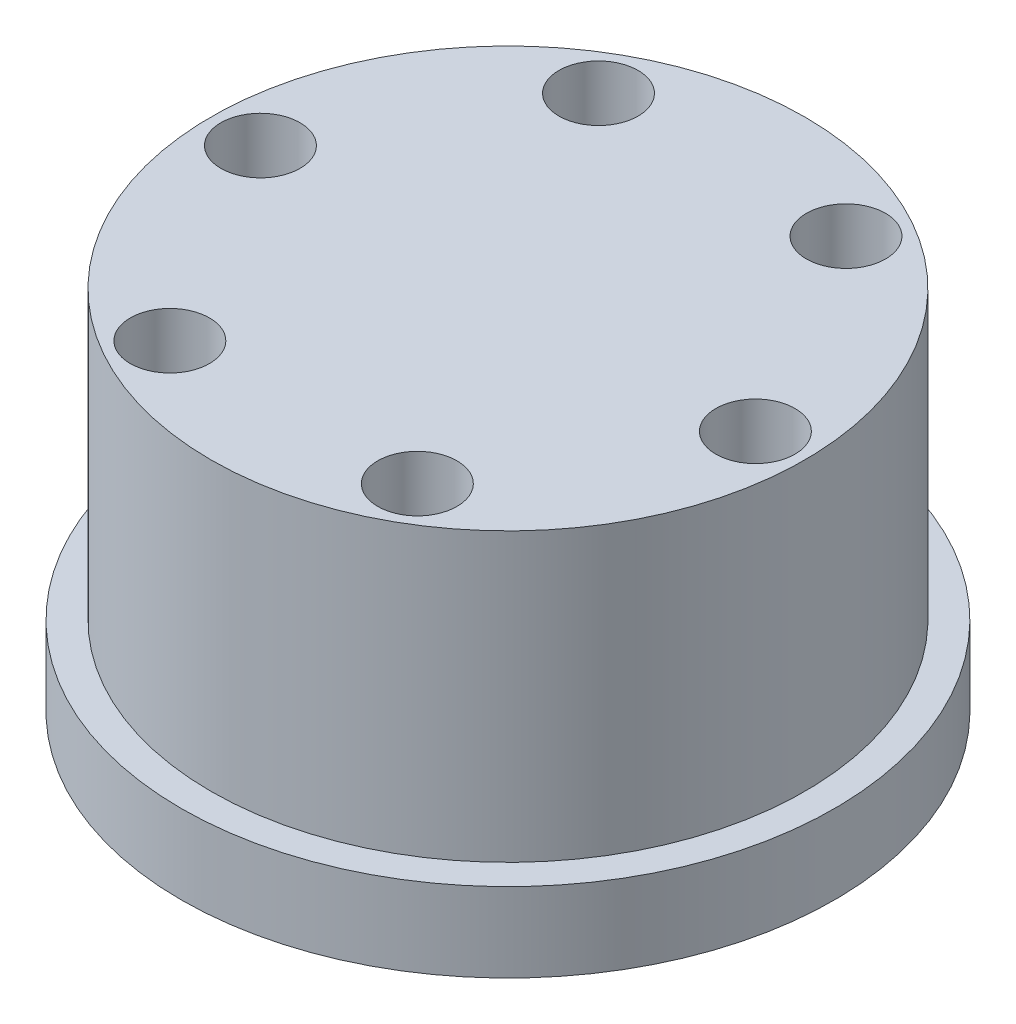
SolidWorks part; units mm, degrees
ref_plane "Front Plane" through (0, 0, 0) normal (0, 0, 1) x (1, 0, 0)
ref_plane "Top Plane" through (0, 0, 0) normal (0, 1, 0) x (1, 0, 0)
ref_plane "Right Plane" through (0, 0, 0) normal (1, 0, 0) x (0, 0, -1)
sketch "Sketch1" plane through (0, 0, 0) normal (0, 1, 0) x (1, 0, 0)
  circle A0 centre (0, 0) radius 16.5
  circle A1 centre (0, 0) radius 12.5 construction
  circle A2 centre (0, 12.5) radius 1.5
  circle A3 centre (10.8253, 6.25) radius 1.5
  circle A4 centre (10.8253, -6.25) radius 1.5
  circle A5 centre (0, -12.5) radius 1.5
  circle A6 centre (-10.8253, -6.25) radius 1.5
  circle A7 centre (-10.8253, 6.25) radius 1.5
  point P19 (0, 0)
  dimension "D1" = 33
  dimension "D2" = 25
  dimension "D3" = 3
  dimension "D4" = 6
extrude "Boss-Extrude1" add sketch "Sketch1" along normal blind 4
sketch "Sketch2" plane through (0, 4, 0) normal (0, 1, 0) x (1, 0, 0)
  circle A0 centre (0, 0) radius 15
  dimension "D1" = 30
extrude "Boss-Extrude2" add sketch "Sketch2" along normal blind 14.5
sketch "Sketch5" plane through (0, 18.5, 0) normal (0, 1, 0) x (1, 0, 0)
  circle A0 centre (0, 0) radius 12.5 construction
  circle A1 centre (-12.5, 0) radius 2
  circle A2 centre (-6.25, 10.8253) radius 2
  circle A3 centre (6.25, 10.8253) radius 2
  circle A4 centre (12.5, 0) radius 2
  circle A5 centre (6.25, -10.8253) radius 2
  circle A6 centre (-6.25, -10.8253) radius 2
  point P17 (0, 0)
  dimension "D1" = 25
  dimension "D2" = 4
  dimension "D3" = 6
extrude "Cut-Extrude3" cut sketch "Sketch5" against normal blind 6.5
sketch "Sketch6" plane through (0, 0, 0) normal (0, -1, 0) x (1, 0, 0)
  circle A0 centre (0, 0) radius 7.5
  dimension "D1" = 15
extrude "Cut-Extrude4" cut sketch "Sketch6" against normal blind 4
